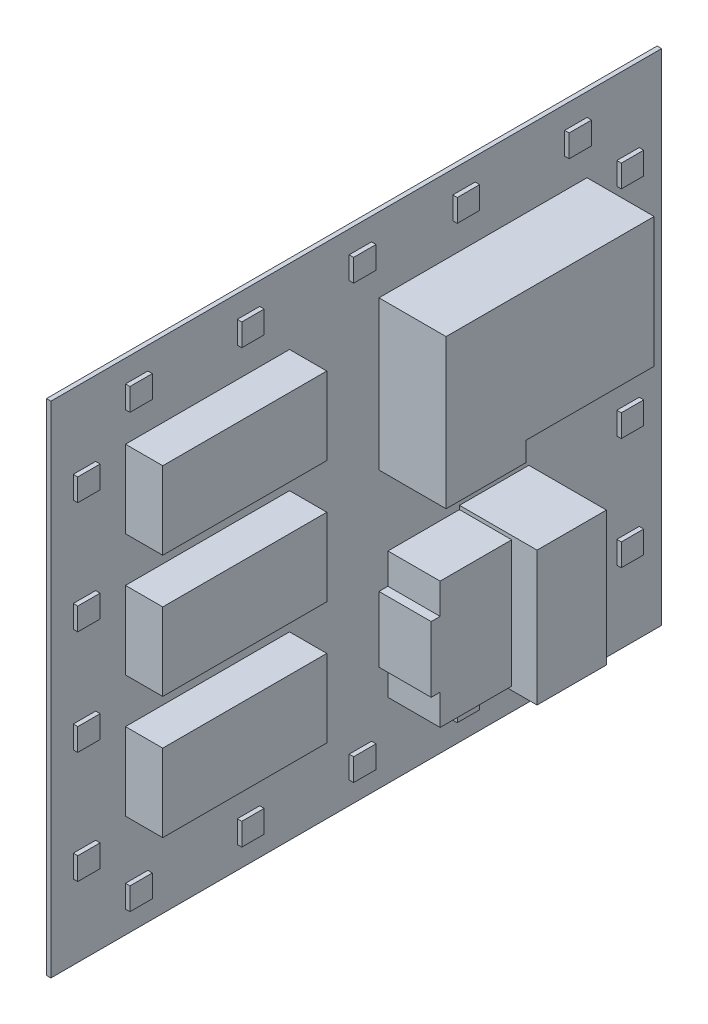
SolidWorks part; units mm, degrees
material "ABS"
ref_plane "Front Plane" through (0, 0, 0) normal (0, 0, 1) x (1, 0, 0)
ref_plane "Top Plane" through (0, 0, 0) normal (0, 1, 0) x (1, 0, 0)
ref_plane "Right Plane" through (0, 0, 0) normal (1, 0, 0) x (0, 0, -1)
sketch "Sketch1" plane through (0, 0, 0) normal (1, 0, 0) x (0, 0, -1)
  line L0 (-220, 150) -> (189.5, 150)
  line L1 (83.5, 100) -> (139.5, 100)
  line L2 (83.5, 100) -> (83.5, 13)
  line L3 (83.5, 13) -> (139.5, 13)
  line L4 (139.5, 100) -> (139.5, 13)
  line L5 (83.5, 100) -> (139.5, 13) construction
  line L6 (83.5, 13) -> (139.5, 100) construction
  line L7 (0, 100) -> (53.5, 100)
  line L8 (0, 100) -> (0, 0)
  line L9 (0, 0) -> (53.5, 0)
  line L10 (53.5, 100) -> (53.5, 0)
  line L11 (0, 100) -> (53.5, 0) construction
  line L12 (0, 0) -> (53.5, 100) construction
  line L13 (-60, 100) -> (-170, 100)
  line L14 (-60, 100) -> (-60, 48)
  line L15 (-60, 48) -> (-170, 48)
  line L16 (-170, 100) -> (-170, 48)
  line L17 (-60, 100) -> (-170, 48) construction
  line L18 (-60, 48) -> (-170, 100) construction
  line L19 (-170, 18) -> (-60, 18)
  line L20 (-170, 18) -> (-170, -34)
  line L21 (-170, -34) -> (-60, -34)
  line L22 (-60, 18) -> (-60, -34)
  line L23 (-170, 18) -> (-60, -34) construction
  line L24 (-170, -34) -> (-60, 18) construction
  line L25 (-170, -64) -> (-60, -64)
  line L26 (-170, -64) -> (-170, -116)
  line L27 (-170, -116) -> (-60, -116)
  line L28 (-60, -64) -> (-60, -116)
  line L29 (-170, -64) -> (-60, -116) construction
  line L30 (-170, -116) -> (-60, -64) construction
  line L31 (6, -50) -> (54, -50)
  line L32 (6, -50) -> (6, -135)
  line L33 (6, -135) -> (54, -135)
  line L34 (54, -50) -> (54, -135)
  line L35 (6, -50) -> (54, -135) construction
  line L36 (6, -135) -> (54, -50) construction
  line L37 (0, -70.5) -> (6, -70.5)
  line L38 (0, -70.5) -> (0, -114.5)
  line L39 (0, -114.5) -> (6, -114.5)
  line L40 (6, -70.5) -> (6, -114.5)
  line L41 (0, -70.5) -> (6, -114.5) construction
  line L42 (0, -114.5) -> (6, -70.5) construction
  line L43 (54, -47.5) -> (100.5, -47.5)
  line L44 (54, -47.5) -> (54, -137.5)
  line L45 (54, -137.5) -> (100.5, -137.5)
  line L46 (100.5, -47.5) -> (100.5, -137.5)
  line L47 (54, -47.5) -> (100.5, -137.5) construction
  line L48 (54, -137.5) -> (100.5, -47.5) construction
  line L49 (100.5, -70.5) -> (106.5, -70.5)
  line L50 (100.5, -70.5) -> (100.5, -114.5)
  line L51 (100.5, -114.5) -> (106.5, -114.5)
  line L52 (106.5, -70.5) -> (106.5, -114.5)
  line L53 (100.5, -70.5) -> (106.5, -114.5) construction
  line L54 (100.5, -114.5) -> (106.5, -70.5) construction
  line L55 (189.5, 150) -> (189.5, -185)
  line L56 (189.5, -185) -> (-220, -185)
  line L57 (-220, -185) -> (-220, 150)
  line L58 (53.5, 100) -> (83.5, 100)
  line L59 (83.5, 13) -> (53.5, 13)
  line L61 (-205, 100) -> (-190, 100)
  line L62 (-205, 100) -> (-205, 85)
  line L63 (-205, 85) -> (-190, 85)
  line L64 (-190, 100) -> (-190, 85)
  line L65 (-205, 100) -> (-190, 85) construction
  line L66 (-205, 85) -> (-190, 100) construction
  line L67 (-205, -135) -> (-190, -135)
  line L68 (-205, -135) -> (-205, -120)
  line L69 (-205, -120) -> (-190, -120)
  line L70 (-190, -135) -> (-190, -120)
  line L71 (-205, -135) -> (-190, -120) construction
  line L72 (-205, -120) -> (-190, -135) construction
  line L73 (-205, -60) -> (-190, -60)
  line L74 (-205, -60) -> (-205, -45)
  line L75 (-205, -45) -> (-190, -45)
  line L76 (-190, -60) -> (-190, -45)
  line L77 (-205, -60) -> (-190, -45) construction
  line L78 (-205, -45) -> (-190, -60) construction
  line L79 (-205, 10) -> (-190, 10)
  line L80 (-205, 10) -> (-205, 25)
  line L81 (-205, 25) -> (-190, 25)
  line L82 (-190, 10) -> (-190, 25)
  line L83 (-205, 10) -> (-190, 25) construction
  line L84 (-205, 25) -> (-190, 10) construction
  line L85 (-170, -170) -> (-155, -170)
  line L86 (-170, -170) -> (-170, -155)
  line L87 (-170, -155) -> (-155, -155)
  line L88 (-155, -170) -> (-155, -155)
  line L89 (-170, -170) -> (-155, -155) construction
  line L90 (-170, -155) -> (-155, -170) construction
  line L91 (-95, -170) -> (-80, -170)
  line L92 (-95, -170) -> (-95, -155)
  line L93 (-95, -155) -> (-80, -155)
  line L94 (-80, -170) -> (-80, -155)
  line L95 (-95, -170) -> (-80, -155) construction
  line L96 (-95, -155) -> (-80, -170) construction
  line L97 (-20, -170) -> (-5, -170)
  line L98 (-20, -170) -> (-20, -155)
  line L99 (-20, -155) -> (-5, -155)
  line L100 (-5, -170) -> (-5, -155)
  line L101 (-20, -170) -> (-5, -155) construction
  line L102 (-20, -155) -> (-5, -170) construction
  line L103 (139.5, -170) -> (124.5, -170)
  line L104 (139.5, -170) -> (139.5, -155)
  line L105 (139.5, -155) -> (124.5, -155)
  line L106 (124.5, -170) -> (124.5, -155)
  line L107 (139.5, -170) -> (124.5, -155) construction
  line L108 (139.5, -155) -> (124.5, -170) construction
  line L109 (64.5, -170) -> (49.5, -170)
  line L110 (64.5, -170) -> (64.5, -155)
  line L111 (64.5, -155) -> (49.5, -155)
  line L112 (49.5, -170) -> (49.5, -155)
  line L113 (64.5, -170) -> (49.5, -155) construction
  line L114 (64.5, -155) -> (49.5, -170) construction
  line L115 (174.5, 100) -> (159.5, 100)
  line L116 (174.5, 100) -> (174.5, 85)
  line L117 (174.5, 85) -> (159.5, 85)
  line L118 (159.5, 100) -> (159.5, 85)
  line L119 (174.5, 100) -> (159.5, 85) construction
  line L120 (174.5, 85) -> (159.5, 100) construction
  line L121 (174.5, 25) -> (159.5, 25)
  line L122 (174.5, 25) -> (174.5, 10)
  line L123 (174.5, 10) -> (159.5, 10)
  line L124 (159.5, 25) -> (159.5, 10)
  line L125 (174.5, 25) -> (159.5, 10) construction
  line L126 (174.5, 10) -> (159.5, 25) construction
  line L127 (174.5, -45) -> (159.5, -45)
  line L128 (174.5, -45) -> (174.5, -60)
  line L129 (174.5, -60) -> (159.5, -60)
  line L130 (159.5, -45) -> (159.5, -60)
  line L131 (174.5, -45) -> (159.5, -60) construction
  line L132 (174.5, -60) -> (159.5, -45) construction
  line L133 (174.5, -120) -> (159.5, -120)
  line L134 (174.5, -120) -> (174.5, -135)
  line L135 (174.5, -135) -> (159.5, -135)
  line L136 (159.5, -120) -> (159.5, -135)
  line L137 (174.5, -120) -> (159.5, -135) construction
  line L138 (174.5, -135) -> (159.5, -120) construction
  line L139 (-170, 135) -> (-155, 135)
  line L140 (-170, 135) -> (-170, 120)
  line L141 (-170, 120) -> (-155, 120)
  line L142 (-155, 135) -> (-155, 120)
  line L143 (-170, 135) -> (-155, 120) construction
  line L144 (-170, 120) -> (-155, 135) construction
  line L145 (-95, 135) -> (-80, 135)
  line L146 (-95, 135) -> (-95, 120)
  line L147 (-95, 120) -> (-80, 120)
  line L148 (-80, 135) -> (-80, 120)
  line L149 (-95, 135) -> (-80, 120) construction
  line L150 (-95, 120) -> (-80, 135) construction
  line L151 (49.5, 135) -> (64.5, 135)
  line L152 (49.5, 135) -> (49.5, 120)
  line L153 (49.5, 120) -> (64.5, 120)
  line L154 (64.5, 135) -> (64.5, 120)
  line L155 (49.5, 135) -> (64.5, 120) construction
  line L156 (49.5, 120) -> (64.5, 135) construction
  line L157 (124.5, 135) -> (139.5, 135)
  line L158 (124.5, 135) -> (124.5, 120)
  line L159 (124.5, 120) -> (139.5, 120)
  line L160 (139.5, 135) -> (139.5, 120)
  line L161 (124.5, 135) -> (139.5, 120) construction
  line L162 (124.5, 120) -> (139.5, 135) construction
  line L163 (-20, 135) -> (-5, 135)
  line L164 (-20, 135) -> (-20, 120)
  line L165 (-20, 120) -> (-5, 120)
  line L166 (-5, 135) -> (-5, 120)
  line L167 (-20, 135) -> (-5, 120) construction
  line L168 (-20, 120) -> (-5, 135) construction
  point P4 (111.5, 56.5)
  point P10 (26.75, 50)
  point P17 (-115, 74)
  point P19 (-115, -8)
  point P24 (-115, -90)
  point P30 (30, -92.5)
  point P31 (6, -92.5)
  point P36 (3, -92.5)
  point P37 (6, -92.5)
  point P38 (54, -92.5)
  point P43 (77.25, -92.5)
  point P44 (100.5, -92.5)
  point P49 (103.5, -92.5)
  point P50 (100.5, -92.5)
  point P60 (-197.5, 92.5)
  point P65 (-197.5, -127.5)
  point P70 (-197.5, -52.5)
  point P75 (-197.5, 17.5)
  point P80 (-162.5, -162.5)
  point P85 (-87.5, -162.5)
  point P90 (-12.5, -162.5)
  point P95 (132, -162.5)
  point P100 (57, -162.5)
  point P105 (167, 92.5)
  point P110 (167, 17.5)
  point P115 (167, -52.5)
  point P120 (167, -127.5)
  point P125 (-162.5, 127.5)
  point P130 (-87.5, 127.5)
  point P135 (57, 127.5)
  point P140 (132, 127.5)
  point P146 (167, 100)
  point P151 (-12.5, 127.5)
  dimension "D1" = 56
  dimension "D2" = 87
  dimension "D3" = 100
  dimension "D4" = 53.5
  dimension "D5" = 30
  dimension "D6" = 110
  dimension "D7" = 52
  dimension "D8" = 30
  dimension "D9" = 30
  dimension "D10" = 60
  dimension "D11" = 85
  dimension "D12" = 48
  dimension "D13" = 6
  dimension "D14" = 44
  dimension "D15" = 46.5
  dimension "D16" = 90
  dimension "D17" = 6
  dimension "D18" = 44
  dimension "D19" = 50
  dimension "D20" = 50
  dimension "D21" = 50
  dimension "D22" = 50
  dimension "D23" = 50
  dimension "D24" = 15
  dimension "D25" = 15
  dimension "D26" = 15
  dimension "D27" = 50
  dimension "D28" = 15
  dimension "D29" = 15
  dimension "D30" = 15
  dimension "D31" = 50
  dimension "D32" = 50
  dimension "D33" = 50
  dimension "D34" = 50
  dimension "D35" = 50
  dimension "D36" = 50
  dimension "D37" = 50
  dimension "D38" = 75
  dimension "D39" = 75
  dimension "D40" = 75
  dimension "D41" = 75
  dimension "D42" = 75
  dimension "D43" = 75
  dimension "D44" = 75
  dimension "D45" = 75
  dimension "D46" = 75
  dimension "D47" = 75
extrude "Boss-Extrude1" add sketch "Sketch1" along normal blind 3 contours L57 L56 L55 L0 L16 L13 L14 L15 L1 L4 L3 L2 L7 L10 L9 L8 L19 L22 L21 L20 L25 L28 L27 L26 L49 L52 L51 L46 L45 L34 L33 L32 L39 L38 L37 L31 L43 | L13 L16 L15 L14 | L10 L7 L8 L9 | L4 L1 L2 L3 | L46 L43 L34 L45 | L22 L19 L20 L21 | L28 L25 L26 L27 | L52 L49 L46 L51 | L34 L31 L32 L33 | L38 L39 L32 L37 | L59 L2 L58 L10 | L67 L70 L69 L68 | L85 L88 L87 L86 | L91 L94 L93 L92 | L97 L100 L99 L98 | L112 L109 L110 L111 | L73 L76 L75 L74 | L79 L82 L81 L80 | L64 L61 L62 L63 | L142 L139 L140 L141 | L148 L145 L146 L147 | L166 L163 L164 L165 | L154 L151 L152 L153 | L106 L103 L104 L105 | L127 L130 L129 L128 | L121 L124 L123 L122 | L115 L118 L117 L116 | L160 L157 L158 L159 | L136 L135 L134 L133 region at (0, -21.934, 14.8074) region at (0, 56.5, -111.5) region at (0, 56.5, -68.5) region at (0, 50, -26.75) region at (0, 74, 115) region at (0, -8, 115) region at (0, -90, 115) region at (0, -92.5, -30) region at (0, -92.5, -77.25) region at (0, -92.5, -3) region at (0, -92.5, -103.5) region at (0, 92.5, 197.5) region at (0, -127.5, 197.5) region at (0, -52.5, 197.5) region at (0, 17.5, 197.5) region at (0, -162.5, 162.5) region at (0, -162.5, 87.5) region at (0, -162.5, 12.5) region at (0, -162.5, -132) region at (0, -162.5, -57) region at (0, 92.5, -167) region at (0, 17.5, -167) region at (0, -52.5, -167) region at (0, 127.5, 162.5) region at (0, 127.5, 87.5) region at (0, 127.5, -57) region at (0, 127.5, -132) region at (0, 127.5, 12.5)
extrude "Boss-Extrude2" add sketch "Sketch1<3>" along normal blind 28 contours L13 L16 L15 L14 | L22 L19 L20 L21 | L28 L25 L26 L27 region at (0, 74, 115) region at (0, -8, 115) region at (0, -90, 115)
sketch "Sketch1<3>" plane through (0, 0, 0) normal (1, 0, 0) x (0, 0, -1) same geometry as "Sketch1"
extrude "Boss-Extrude3" add sketch "Sketch1<6>" along normal blind 48 contours L10 L7 L8 L9 | L59 L2 L58 L10 | L4 L1 L2 L3 region at (0, 56.5, -111.5) region at (0, 56.5, -68.5) region at (0, 50, -26.75)
sketch "Sketch1<6>" plane through (0, 0, 0) normal (1, 0, 0) x (0, 0, -1) same geometry as "Sketch1"
extrude "Boss-Extrude4" add sketch "Sketch1<7>" along normal blind 38 contours L34 L31 L32 L33 region at (0, -92.5, -30)
sketch "Sketch1<7>" plane through (0, 0, 0) normal (1, 0, 0) x (0, 0, -1) same geometry as "Sketch1"
extrude "Boss-Extrude5" add sketch "Sketch1<8>" along normal blind 55 contours L46 L43 L44 L34 L45 region at (0, -92.5, -77.25)
sketch "Sketch1<8>" plane through (0, 0, 0) normal (1, 0, 0) x (0, 0, -1) same geometry as "Sketch1"
extrude "Boss-Extrude6" add sketch "Sketch1<9>" along normal blind 38 contours L52 L49 L46 L51 | L38 L39 L32 L37 region at (0, -92.5, -3) region at (0, -92.5, -103.5)
sketch "Sketch1<9>" plane through (0, 0, 0) normal (1, 0, 0) x (0, 0, -1) same geometry as "Sketch1"
extrude "Boss-Extrude7" add sketch "Sketch1<10>" along normal blind 6 contours L64 L63 L62 L61 | L142 L141 L140 L139 | L148 L147 L146 L145 | L166 L165 L164 L163 | L154 L153 L152 L151 | L160 L159 L158 L157 | L116 L117 L118 L115 | L122 L123 L124 L121 | L128 L129 L130 L127 | L134 L135 L136 L133 | L103 L106 L105 L104 | L109 L112 L111 L110 | L97 L100 L99 L98 | L91 L94 L93 L92 | L85 L88 L87 L86 | L67 L70 L69 L68 | L73 L76 L75 L74 | L79 L82 L81 L80
sketch "Sketch1<10>" plane through (0, 0, 0) normal (1, 0, 0) x (0, 0, -1) same geometry as "Sketch1"
